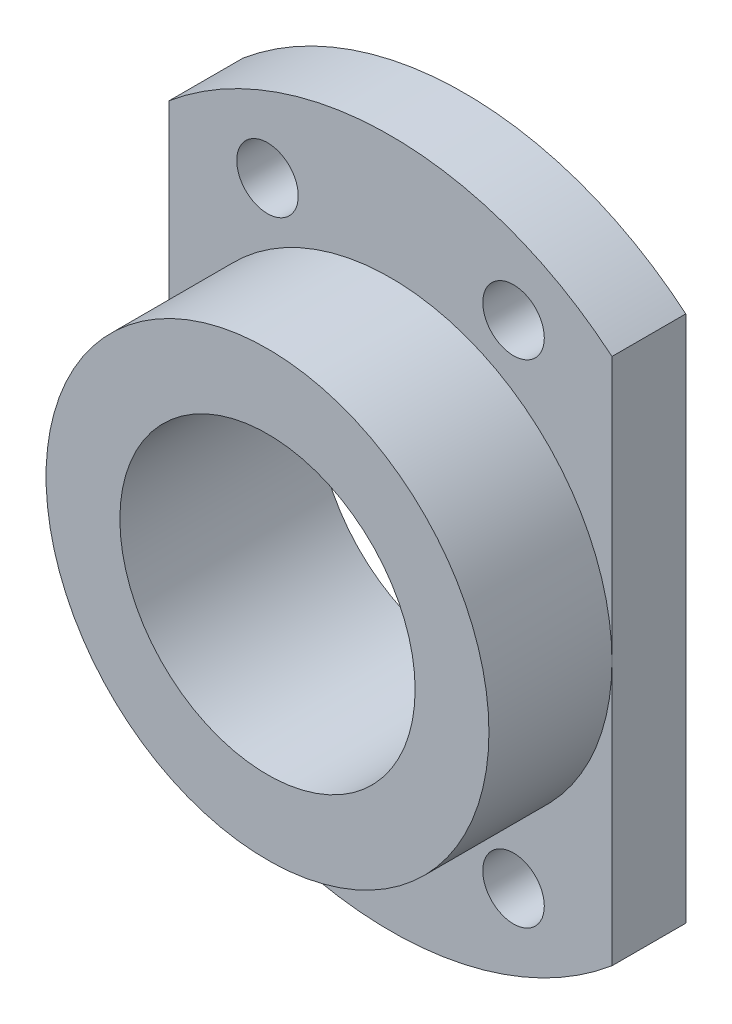
SolidWorks part; units mm, degrees
ref_plane "Front Plane" through (0, 0, 0) normal (0, 0, 1) x (1, 0, 0)
ref_plane "Top Plane" through (0, 0, 0) normal (0, 1, 0) x (1, 0, 0)
ref_plane "Right Plane" through (0, 0, 0) normal (1, 0, 0) x (0, 0, -1)
sketch "Sketch1" plane through (0, 0, 0) normal (0, 0, 1) x (1, 0, 0)
  line L0 (-9, 10.7238) -> (-9, -10.7238)
  line L1 (9, 10.7238) -> (9, -10.7238)
  line L2 (-9, 0) -> (9, 0) construction
  line L3 (-5, 10) -> (5, -10) construction
  line L4 (-5, -10) -> (5, 10) construction
  arc A0 (9, 10.7238) -> (-9, 10.7238) centre (0, 0) ccw
  arc A1 (-9, -10.7238) -> (9, -10.7238) centre (0, 0) ccw
  circle A2 centre (0, 0) radius 6
  circle A3 centre (-5, 10) radius 1.25
  circle A4 centre (5, 10) radius 1.25
  circle A5 centre (-5, -10) radius 1.25
  circle A6 centre (5, -10) radius 1.25
  point P7 (0, 0)
  point P18 (0, 0)
  dimension "D2" = 14
  dimension "D3" = 12
  dimension "D6" = 2.5
  dimension "D1" = 18
  dimension "D4" = 20
  dimension "D5" = 10
extrude "Boss-Extrude1" add sketch "Sketch1" along normal blind 3
sketch "Sketch2" plane through (0, 0, 3) normal (0, 0, 1) x (1, 0, 0)
  circle A0 centre (0, 0) radius 9
  circle A1 centre (0, 0) radius 6
  circle A2 centre (0, 0) radius 6 construction
  dimension "D1" = 18
extrude "LinearBallSupport" add sketch "Sketch2" along normal blind 5
